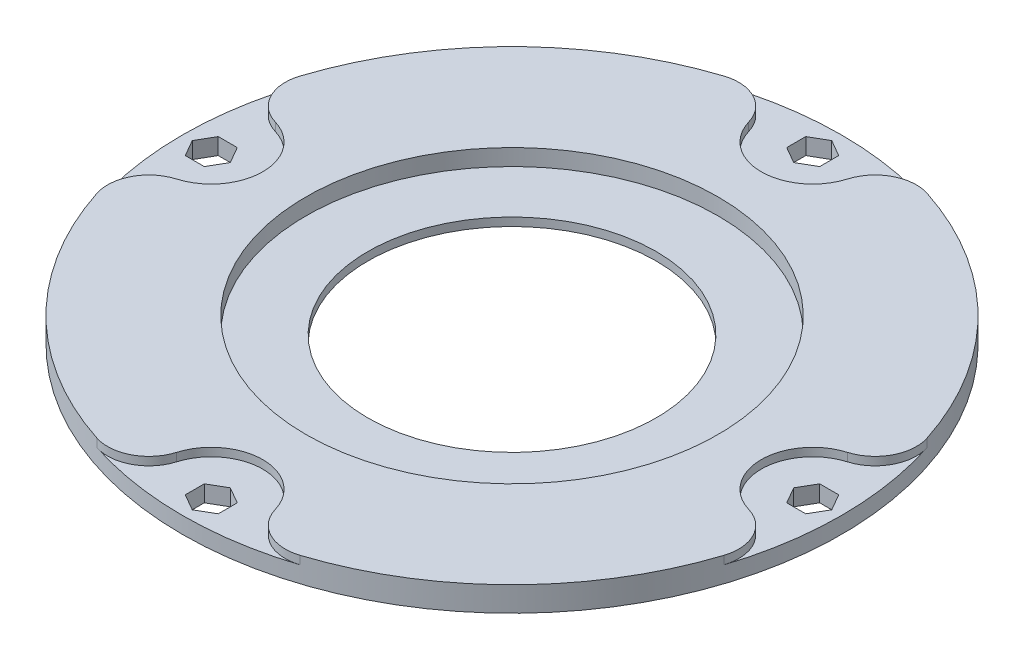
SolidWorks part; units mm, degrees
ref_plane "Front Plane" through (0, 0, 0) normal (0, 0, 1) x (1, 0, 0)
ref_plane "Top Plane" through (0, 0, 0) normal (0, 1, 0) x (1, 0, 0)
ref_plane "Right Plane" through (0, 0, 0) normal (1, 0, 0) x (0, 0, -1)
sketch "Sketch1" plane through (0, 0, 0) normal (0, 1, 0) x (1, 0, 0)
  circle A0 centre (0, 0) radius 80
  circle A1 centre (0, 0) radius 50
  dimension "D1" = 160
  dimension "D2" = 100
extrude "Boss-Extrude1" add sketch "Sketch1" along normal blind 2
sketch "Sketch2" plane through (0, 0, 0) normal (0, -1, 0) x (1, 0, 0)
  circle A0 centre (0, 0) radius 80
  circle A1 centre (0, 0) radius 35
  dimension "D1" = 160
  dimension "D2" = 70
extrude "Boss-Extrude2" add sketch "Sketch2" along normal blind 4
sketch "Sketch3" plane through (0, 2, 0) normal (0, 1, 0) x (1, 0, 0)
  line L0 (0, 73) -> (0, 0) construction
  line L1 (73, 0) -> (0, 0) construction
  line L2 (0, -73) -> (0, 0) construction
  line L3 (-73, 0) -> (0, 0) construction
  circle A0 centre (0, 73) radius 12.5
  circle A2 centre (73, 0) radius 12.5
  circle A3 centre (0, -73) radius 12.5
  circle A4 centre (-73, 0) radius 12.5
  point P16 (0, 0)
  dimension "D1" = 25
  dimension "D3" = 73
  dimension "D2" = 4
extrude "Cut-Extrude1" cut sketch "Sketch3" against normal blind 2
fillet "Fillet1" radius 10 8 edges at (79.2654, 1, 10.8164) (79.2654, 1, -10.8164) (10.8164, 1, 79.2654) (-10.8164, 1, 79.2654) (-79.2654, 1, -10.8164) (-79.2654, 1, 10.8164) (10.8164, 1, -79.2654) (-10.8164, 1, -79.2654)
sketch "Sketch4" plane through (0, 0, 0) normal (0, 1, 0) x (1, 0, 0)
  line L0 (0, 60.5) -> (0, 73) construction
  line L1 (-4, 73) -> (4, 73) construction
  line L2 (-4, 70.6906) -> (-4, 75.3094)
  line L3 (4, 70.6906) -> (4, 75.3094)
  line L4 (2, 76.4641) -> (-2, 69.5359) construction
  line L5 (0, 77.6188) -> (4, 75.3094)
  line L6 (-4, 70.6906) -> (0, 68.3812)
  line L7 (2, 69.5359) -> (-2, 76.4641) construction
  line L8 (4, 70.6906) -> (0, 68.3812)
  line L9 (0, 77.6188) -> (-4, 75.3094)
  line L10 (60.5, 0) -> (73, 0) construction
  line L11 (70.6906, -4) -> (68.3812, 0)
  line L12 (69.5359, -2) -> (76.4641, 2) construction
  line L13 (73, 4) -> (73, -4) construction
  line L14 (70.6906, -4) -> (75.3094, -4)
  line L15 (77.6188, 0) -> (75.3094, -4)
  line L16 (76.4641, -2) -> (69.5359, 2) construction
  line L17 (77.6188, 0) -> (75.3094, 4)
  line L18 (70.6906, 4) -> (75.3094, 4)
  line L19 (70.6906, 4) -> (68.3812, 0)
  line L20 (0, -60.5) -> (0, -73) construction
  line L21 (-4, -70.6906) -> (0, -68.3812)
  line L22 (-2, -69.5359) -> (2, -76.4641) construction
  line L23 (4, -73) -> (-4, -73) construction
  line L24 (-4, -70.6906) -> (-4, -75.3094)
  line L25 (0, -77.6188) -> (-4, -75.3094)
  line L26 (-2, -76.4641) -> (2, -69.5359) construction
  line L27 (0, -77.6188) -> (4, -75.3094)
  line L28 (4, -70.6906) -> (4, -75.3094)
  line L29 (4, -70.6906) -> (0, -68.3812)
  line L30 (-60.5, 0) -> (-73, 0) construction
  line L31 (-70.6906, 4) -> (-68.3812, 0)
  line L32 (-69.5359, 2) -> (-76.4641, -2) construction
  line L33 (-73, -4) -> (-73, 4) construction
  line L34 (-70.6906, 4) -> (-75.3094, 4)
  line L35 (-77.6188, 0) -> (-75.3094, 4)
  line L36 (-76.4641, 2) -> (-69.5359, -2) construction
  line L37 (-77.6188, 0) -> (-75.3094, -4)
  line L38 (-70.6906, -4) -> (-75.3094, -4)
  line L39 (-70.6906, -4) -> (-68.3812, 0)
  arc A0 (-11.9827, 69.4412) -> (11.9827, 69.4412) centre (0, 73) ccw construction
  point P9 (0, 73)
  point P12 (-4, 73)
  point P15 (4, 73)
  point P29 (0, 73)
  point P67 (0, 0)
  dimension "D1" = 3
  dimension "D2" = 8
  dimension "D4" = 60.5
  dimension "D3" = 4
extrude "Cut-Extrude2" cut sketch "Sketch4" against normal through all
other "Move Face1" flip direction yes face at (0, 0, -35) offset 2 parameters "D1"=2
